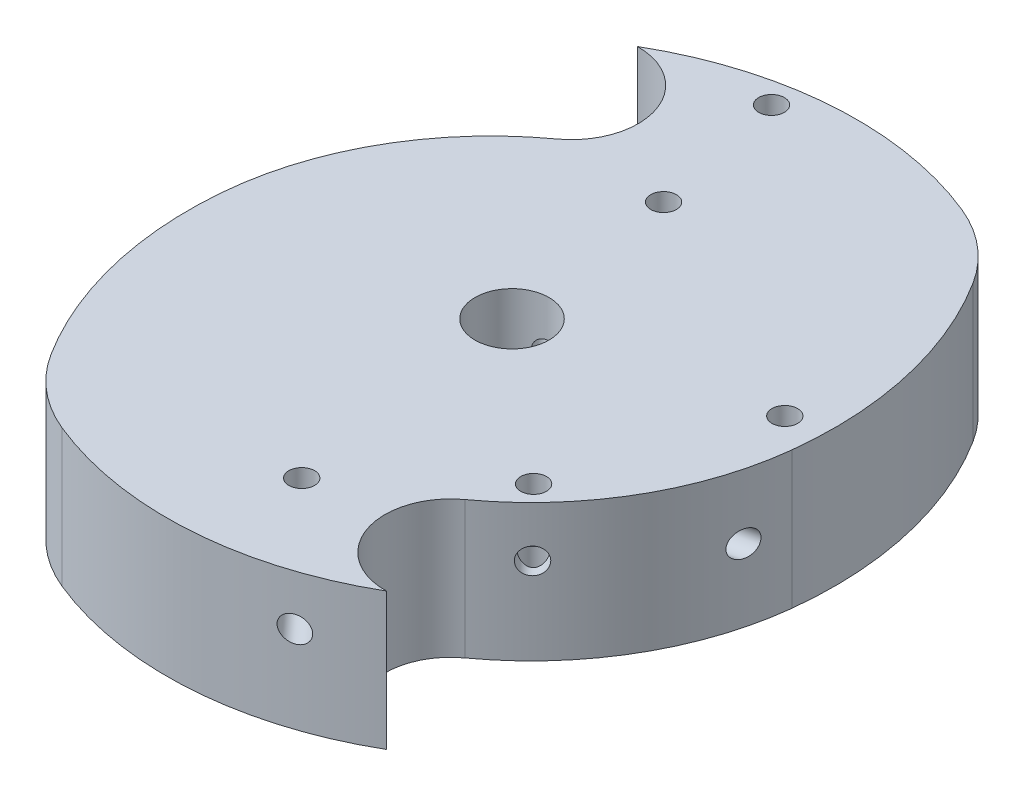
SolidWorks part; units mm, degrees
material "Copper"
ref_plane "Front Plane" through (0, 0, 0) normal (0, 0, 1) x (1, 0, 0)
ref_plane "Top Plane" through (0, 0, 0) normal (0, 1, 0) x (1, 0, 0)
ref_plane "Right Plane" through (0, 0, 0) normal (1, 0, 0) x (0, 0, -1)
other "Center of Mass"
sketch "Sketch1" plane through (0, 0, 0) normal (0, 1, 0) x (1, 0, 0)
  line L2 (0, 0) -> (-3.75, 6.4952)
  line L7 (-3.7617, 6.4884) -> (3.7617, -6.4884)
  arc A0 (-26.445, -64.7925) -> (35.0994, -60.5428) centre (0, 0) ccw
  circle A1 centre (0, 0) radius 7.5
  arc A2 (26.445, 64.7925) -> (-35.0994, 60.5428) centre (0, 0) ccw
  arc A3 (40.4687, 53.0436) -> (51.4109, 5.338) centre (-21.8968, 13.6312) cw
  arc A4 (-40.4687, -53.0436) -> (-51.6091, -7.3323) centre (21.8968, -13.6312) cw
  arc A5 (-26.445, -64.7925) -> (-40.4687, -53.0436) centre (-15.1084, -37.0169) cw
  arc A6 (40.4687, 53.0436) -> (26.445, 64.7925) centre (15.1084, 37.0169) ccw
  arc A13 (-27.0376, 36.1278) -> (-35.0994, 60.5428) centre (-34.9547, 47.0521) ccw
  arc A17 (35.0994, -60.5428) -> (26.985, -36.5115) centre (34.7746, -47.2669) cw
  arc A18 (-27.0376, 36.1278) -> (-51.6091, -7.3323) centre (8.1718, -12.4551) ccw
  arc A19 (26.985, -36.5115) -> (51.4109, 5.338) centre (-8.2088, 12.0827) ccw
  point P10 (0, 0)
  point P13 (0, 0)
  point P15 (0, 0)
  point P26 (0, 0)
  point P35 (0, 0)
  point P39 (0, 0)
  point P43 (0, 0)
  dimension "D1" = 60
  dimension "D2" = 60
extrude "Boss-Extrude1" add sketch "Sketch1" along normal blind 32 contours A3 A6 A2 A4 A5 A0 A1 region at (-33.2554, 0, 58.6776)
scale "Scale1" bodies to scale 101 scale about centroid uniform scaling no x scale factor 1.15 y scale factor 1 z scale factor 1.15
hole_wizard "Ø6.0mm Dowel Hole1" positions "Sketch2" profile "Sketch3" hole size "Ø6.0" standard "ANSI Metric" end condition through all
sketch "Sketch2" plane through (150.5526, -30.7665, -103.6577) normal (0, -1, 0) x (0.9769, 0, -0.2136)
  point P0 (-166.162, -5.4146)
sketch "Sketch3" plane through (-12.9314, -30.7665, -73.4563) normal (1, 0, 0) x (0, 0, -1)
  line L0 (0, 0) -> (0, 62.7665)
  line L1 (0, 62.7665) -> (3, 62.7665)
  line L2 (3, 62.7665) -> (3, 0)
  line L3 (3, 0) -> (0, 0)
  line L4 (0, -6.35) -> (0, 107.95) construction
  dimension "Thru Hole Dia." = 6
  dimension "Thru Hole Depth" = 62.7665
hole_wizard "Ø6.0mm Dowel Hole2" positions "Sketch4" profile "Sketch5" hole size "Ø6.0" standard "ANSI Metric" end condition through all
sketch "Sketch4" plane through (150.5526, -30.7665, -103.6577) normal (0, -1, 0) x (0.9769, 0, -0.2136)
  point P0 (-166.1755, 27.5457)
sketch "Sketch5" plane through (-5.9044, -30.7665, -41.2537) normal (1, 0, 0) x (0, 0, -1)
  line L0 (0, 0) -> (0, 62.7665)
  line L1 (0, 62.7665) -> (3, 62.7665)
  line L2 (3, 62.7665) -> (3, 0)
  line L3 (3, 0) -> (0, 0)
  line L4 (0, -6.35) -> (0, 107.95) construction
  dimension "Thru Hole Dia." = 6
  dimension "Thru Hole Depth" = 62.7665
hole_wizard "Ø6.0mm Dowel Hole4" positions "Sketch8" profile "Sketch9" hole size "Ø6.0" standard "ANSI Metric" end condition through all
sketch "Sketch8" plane through (150.5526, -30.7665, -103.6577) normal (0, -1, 0) x (0.9769, 0, -0.2136)
  point P0 (-116.3613, 68.1913)
sketch "Sketch9" plane through (51.4418, -30.7665, -12.186) normal (1, 0, 0) x (0, 0, -1)
  line L0 (0, 0) -> (0, 62.7665)
  line L1 (0, 62.7665) -> (3, 62.7665)
  line L2 (3, 62.7665) -> (3, 0)
  line L3 (3, 0) -> (0, 0)
  line L4 (0, -6.35) -> (0, 107.95) construction
  dimension "Thru Hole Dia." = 6
  dimension "Thru Hole Depth" = 62.7665
hole_wizard "Ø6.0mm Dowel Hole5" positions "Sketch10" profile "Sketch11" hole size "Ø6.0" standard "AS" end condition through all
sketch "Sketch10" plane through (86.6997, 143.313, -89.6969) normal (0.9769, 0, -0.2136) x (0, 1, 0)
  point P0 (-126.3997, 84.5766)
sketch "Sketch11" plane through (104.7646, 16.9133, -7.0721) normal (0, 1, 0) x (-0.2136, 0, -0.9769)
  line L0 (0, 0) -> (0, 179.3343)
  line L1 (0, 179.3343) -> (3, 179.3343)
  line L2 (3, 179.3343) -> (3, 0)
  line L3 (3, 0) -> (0, 0)
  line L4 (0, -6.35) -> (0, 107.95) construction
  dimension "Thru Hole Dia." = 6
  dimension "Thru Hole Depth" = 179.3343
hole_wizard "Ø6.0mm Dowel Hole6" positions "Sketch12" profile "Sketch13" hole size "Ø6.0" standard "AS" end condition through all
sketch "Sketch12" plane through (150.5526, -30.7665, -103.6577) normal (0, -1, 0) x (0.9769, 0, -0.2136)
  point P0 (-173.8582, 126.1225)
sketch "Sketch13" plane through (7.6455, -30.7665, 56.6892) normal (1, 0, 0) x (0, 0, -1)
  line L0 (0, 0) -> (0, 62.7665)
  line L1 (0, 62.7665) -> (3, 62.7665)
  line L2 (3, 62.7665) -> (3, 0)
  line L3 (3, 0) -> (0, 0)
  line L4 (0, -6.35) -> (0, 107.95) construction
  dimension "Thru Hole Dia." = 6
  dimension "Thru Hole Depth" = 62.7665
hole_wizard "Ø6.0mm Dowel Hole9" positions "Sketch18" profile "Sketch19" hole size "Ø6.0" standard "AS" end condition through all
sketch "Sketch18" plane through (150.5526, -30.7665, -103.6577) normal (0, -1, 0) x (0.9769, 0, -0.2136)
  point P0 (-140.7643, 106.8901)
sketch "Sketch19" plane through (35.8678, -30.7665, 30.8319) normal (1, 0, 0) x (0, 0, -1)
  line L0 (0, 0) -> (0, 62.7665)
  line L1 (0, 62.7665) -> (3, 62.7665)
  line L2 (3, 62.7665) -> (3, 0)
  line L3 (3, 0) -> (0, 0)
  line L4 (0, -6.35) -> (0, 107.95) construction
  dimension "Thru Hole Dia." = 6
  dimension "Thru Hole Depth" = 62.7665
hole_wizard "Ø6.0mm Dowel Hole10" positions "Sketch20" profile "Sketch21" hole size "Ø6.0" standard "ANSI Metric" end condition through all
sketch "Sketch20" plane through (200.7792, 143.313, -48.5447) normal (0.6736, 0, 0.7391) x (0, -1, 0)
  point P0 (123.0979, -175.281)
sketch "Sketch21" plane through (71.2268, 20.2151, 69.5214) normal (0, 1, 0) x (0.7391, 0, -0.6736)
  line L0 (0, 0) -> (0, 199.0352)
  line L1 (0, 199.0352) -> (3, 199.0352)
  line L2 (3, 199.0352) -> (3, 0)
  line L3 (3, 0) -> (0, 0)
  line L4 (0, -6.35) -> (0, 107.95) construction
  dimension "Thru Hole Dia." = 6
  dimension "Thru Hole Depth" = 199.0352
hole_wizard "Ø6.0mm Dowel Hole11" positions "Sketch22" profile "Sketch23" hole size "Ø6.0" standard "ANSI Metric" end condition through all
sketch "Sketch22" plane through (200.7792, 143.313, -48.5447) normal (0.6736, 0, 0.7391) x (0, -1, 0)
  point P0 (123.0262, -213.5355)
sketch "Sketch23" plane through (42.9525, 20.2868, 95.289) normal (0, 1, 0) x (0.7391, 0, -0.6736)
  line L0 (0, 0) -> (0, 199.0352)
  line L1 (0, 199.0352) -> (3, 199.0352)
  line L2 (3, 199.0352) -> (3, 0)
  line L3 (3, 0) -> (0, 0)
  line L4 (0, -6.35) -> (0, 107.95) construction
  dimension "Thru Hole Dia." = 6
  dimension "Thru Hole Depth" = 199.0352
